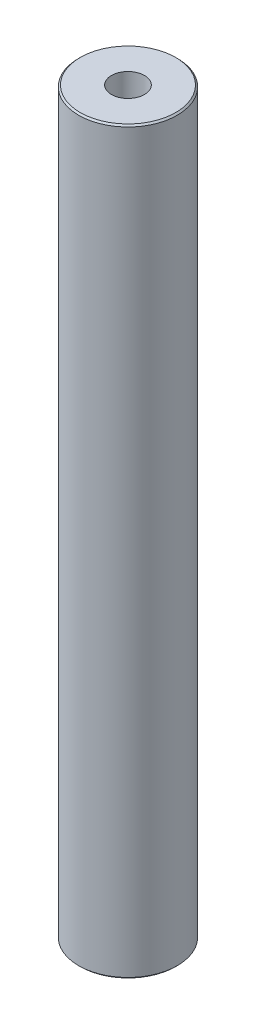
SolidWorks part; units mm, degrees
ref_plane "Front Plane" through (0, 0, 0) normal (0, 0, 1) x (1, 0, 0)
ref_plane "Top Plane" through (0, 0, 0) normal (0, 1, 0) x (1, 0, 0)
ref_plane "Right Plane" through (0, 0, 0) normal (1, 0, 0) x (0, 0, -1)
sketch "Sketch1" plane through (0, 0, 0) normal (0, 1, 0) x (1, 0, 0)
  circle A0 centre (0, 0) radius 40
  dimension "SHAFT_OD" = 80
extrude "Boss-Extrude1" add sketch "Sketch1" along normal blind 600
sketch "Sketch2" plane through (0, 0, 0) normal (0, 1, 0) x (1, 0, 0)
  circle A0 centre (0, 0) radius 13.4101
  dimension "BORE_D" = 26.8202
extrude "Cut-Extrude1" cut sketch "Sketch2" along normal through all
chamfer "Chamfer1" distance 1.2585 angle 45 2 edges at (0, 600, 40) (0, 0, 40)
